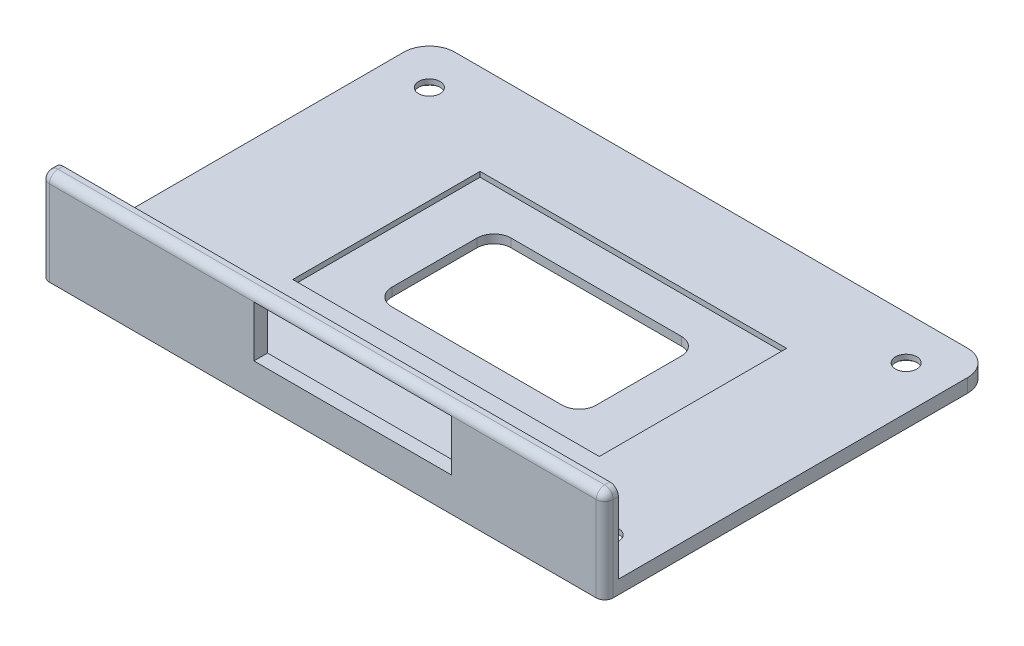
SolidWorks part; units mm, degrees
ref_plane "前视基准面" through (0, 0, 0) normal (0, 0, 1) x (1, 0, 0)
ref_plane "上视基准面" through (0, 0, 0) normal (0, 1, 0) x (1, 0, 0)
ref_plane "右视基准面" through (0, 0, 0) normal (1, 0, 0) x (0, 0, -1)
sketch "草图1" plane through (0, 0, 0) normal (0, 1, 0) x (1, 0, 0)
  line L1 (-33.1, -22) -> (33.1, -22)
  line L2 (-33.1, -22) -> (-33.1, 19)
  line L3 (-30.1, 22) -> (30.1, 22)
  line L4 (33.1, -22) -> (33.1, 19)
  line L5 (-33.1, -22) -> (33.1, 22) construction
  line L6 (-33.1, 22) -> (33.1, -22) construction
  arc A0 (30.1, 22) -> (33.1, 19) centre (30.1, 19) cw
  arc A1 (-33.1, 19) -> (-30.1, 22) centre (-30.1, 19) cw
  point P0 (0, 0)
  dimension "D3" = 3
  dimension "D1" = 44
  dimension "D2" = 66.2
extrude "凸台-拉伸1" add sketch "草图1" along normal blind 1.6
sketch "草图2" plane through (0, 0, 22) normal (0, 0, 1) x (1, 0, 0)
  line L0 (-33.1, 0) -> (33.1, 0)
  line L1 (-33.1, 0) -> (-33.1, 10)
  line L2 (33.1, 0) -> (33.1, 10)
  line L3 (-32.1, 11) -> (-9.1, 11)
  line L5 (-8.1, 10) -> (-8.1, 4)
  line L6 (15.1, 10) -> (15.1, 4)
  line L7 (-8.1, 4) -> (15.1, 4)
  line L8 (17.1, 11) -> (32.1, 11)
  line L9 (-9.1, 11) -> (17.1, 11)
  line L12 (-8.1, 10) -> (15.1, 10)
  arc A0 (33.1, 10) -> (32.1, 11) centre (32.1, 10) ccw
  arc A1 (-33.1, 10) -> (-32.1, 11) centre (-32.1, 10) cw
  point P10 (-33.1, 11)
  dimension "D2" = 1
  dimension "D1" = 11
  dimension "D3" = 7
  dimension "D4" = 25
  dimension "D5" = 18
  dimension "D6" = 6
extrude "封底" add sketch "草图2" along normal blind 1.6
sketch "草图3" plane through (0, 1.6, 0) normal (0, 1, 0) x (1, 0, 0)
  line L1 (-8.5, -7) -> (11.5, -7)
  line L2 (-10.5, -5) -> (-10.5, 5)
  line L3 (-8.5, 7) -> (11.5, 7)
  line L4 (13.5, -5) -> (13.5, 5)
  line L5 (-10.5, -7) -> (13.5, 7) construction
  line L6 (-10.5, 7) -> (13.5, -7) construction
  line L7 (-33.1, -22) -> (33.1, -22) construction
  line L8 (33.1, -22) -> (33.1, 19) construction
  arc A0 (11.5, -7) -> (13.5, -5) centre (11.5, -5) ccw
  arc A1 (-8.5, -7) -> (-10.5, -5) centre (-8.5, -5) cw
  arc A2 (11.5, 7) -> (13.5, 5) centre (11.5, 5) cw
  arc A3 (-10.5, 5) -> (-8.5, 7) centre (-8.5, 5) cw
  point P0 (0, 0)
  dimension "D3" = 2
  dimension "D1" = 24
  dimension "D2" = 14
  dimension "D4" = 19.6
  dimension "D5" = 15
extrude "磁带窗" cut sketch "草图3" against normal up to next
sketch "草图5" plane through (0, 0, 0) normal (0, -1, 0) x (1, 0, 0)
  line L0 (-33.1, -19) -> (-33.1, 23.6) construction
  line L1 (30.1, -22) -> (-30.1, -22) construction
  circle A0 centre (-28, -16.9) radius 2.6
  circle A1 centre (28, -16.9) radius 2.6
  circle A2 centre (28, 18.1) radius 2.6
  circle A3 centre (-28, 18.1) radius 2.6
  point P0 (-28, -16.9)
  point P10 (28, -16.9)
  point P13 (28, 18.1)
  point P16 (-28, 18.1)
  dimension "D3" = 5.2
  dimension "D1" = 5.1
  dimension "D2" = 5.1
  dimension "D4" = 2
  dimension "D5" = 2
extrude "正螺丝孔" cut sketch "草图5" against normal blind 1
sketch "草图7" plane through (0, 1, 0) normal (0, -1, 0) x (1, 0, 0)
  circle A0 centre (-28, -16.9) radius 1.25
  circle A1 centre (28, -16.9) radius 1.25
  circle A2 centre (28, 18.1) radius 1.25
  circle A3 centre (-28, 18.1) radius 1.25
  dimension "D1" = 2.5
  dimension "D2" = 2
  dimension "D3" = 2
extrude "背螺丝孔" cut sketch "草图7" against normal up to next
sketch "草图9" plane through (0, 1.6, 0) normal (0, 1, 0) x (1, 0, 0)
  line L1 (-16.4991, -10.6372) -> (19.5009, -10.6372)
  line L2 (-16.4991, -10.6372) -> (-16.4991, 11.3628)
  line L3 (-16.4991, 11.3628) -> (19.5009, 11.3628)
  line L4 (19.5009, -10.6372) -> (19.5009, 11.3628)
  line L5 (-16.4991, -10.6372) -> (19.5009, 11.3628) construction
  line L6 (-16.4991, 11.3628) -> (19.5009, -10.6372) construction
  point P0 (1.5009, 0.3628)
  dimension "D1" = 36
  dimension "D2" = 22
extrude "屏幕槽" cut sketch "草图9" against normal blind 0.6 contours L2 L1 L4 L3
fillet "圆角2" radius 1 5 edges at (33.1, 5, 23.6) (32.8071, 10.7071, 23.6) (-33.1, 5, 23.6) (-32.8071, 10.7071, 23.6) (0, 11, 23.6)
